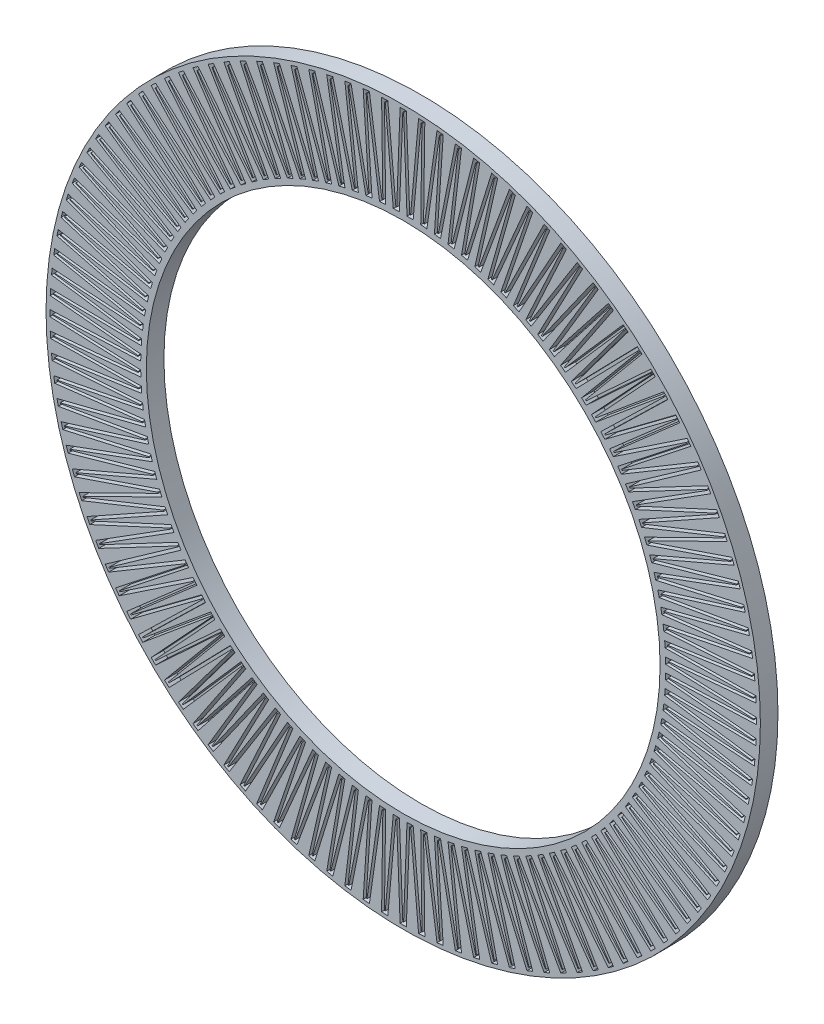
SolidWorks part; units mm, degrees
ref_plane "Front Plane" through (0, 0, 0) normal (0, 0, 1) x (1, 0, 0)
ref_plane "Top Plane" through (0, 0, 0) normal (0, 1, 0) x (1, 0, 0)
ref_plane "Right Plane" through (0, 0, 0) normal (1, 0, 0) x (0, 0, -1)
sketch "Sketch1" plane through (0, 0, 0) normal (0, 0, 1) x (1, 0, 0)
  circle A0 centre (0, 0) radius 203
  circle A1 centre (0, 0) radius 146
extrude "Ring" add sketch "Sketch1" along normal blind 10
ref_plane "Plane_z3" through (0, 0, 3) normal (0, 0, 1) x (1, 0, 0)
sketch "Sketch2" plane through (0, 0, 3) normal (0, 0, 1) x (1, 0, 0)
  line L0 (200.7975, -1.7698) -> (200.7975, 1.7698)
  line L1 (200.7975, 1.7698) -> (150.7515, 3.6974)
  line L2 (150.7515, 3.6974) -> (150.7384, 4.1974)
  line L3 (150.7384, 4.1974) -> (200.6149, 8.7416)
  line L4 (200.6149, 8.7416) -> (200.4297, 12.2763)
  line L5 (200.4297, 12.2763) -> (150.3514, 11.582)
  line L6 (150.3514, 11.582) -> (150.3122, 12.0807)
  line L7 (150.3122, 12.0807) -> (199.8825, 19.229)
  line L8 (199.8825, 19.229) -> (199.5125, 22.7491)
  line L9 (199.5125, 22.7491) -> (149.5392, 19.4349)
  line L10 (149.5392, 19.4349) -> (149.4739, 19.9309)
  line L11 (149.4739, 19.9309) -> (198.6022, 29.6637)
  line L12 (198.6022, 29.6637) -> (198.0485, 33.1596)
  line L13 (198.0485, 33.1596) -> (148.3171, 27.2346)
  line L14 (148.3171, 27.2346) -> (148.226, 27.7265)
  line L15 (148.226, 27.7265) -> (196.7776, 40.017)
  line L16 (196.7776, 40.017) -> (196.0416, 43.4793)
  line L17 (196.0416, 43.4793) -> (146.6885, 34.9596)
  line L18 (146.6885, 34.9596) -> (146.5718, 35.446)
  line L19 (146.5718, 35.446) -> (194.4135, 50.2607)
  line L20 (194.4135, 50.2607) -> (193.4974, 53.6797)
  line L21 (193.4974, 53.6797) -> (144.6579, 42.5887)
  line L22 (144.6579, 42.5887) -> (144.5158, 43.0684)
  line L23 (144.5158, 43.0684) -> (191.5167, 60.3667)
  line L24 (191.5167, 60.3667) -> (190.4229, 63.733)
  line L25 (190.4229, 63.733) -> (142.2307, 50.1012)
  line L26 (142.2307, 50.1012) -> (142.0637, 50.5727)
  line L27 (142.0637, 50.5727) -> (188.0948, 70.3072)
  line L28 (188.0948, 70.3072) -> (186.8264, 73.6116)
  line L29 (186.8264, 73.6116) -> (139.4137, 57.4763)
  line L30 (139.4137, 57.4763) -> (139.2222, 57.9385)
  line L31 (139.2222, 57.9385) -> (184.1575, 80.0549)
  line L32 (184.1575, 80.0549) -> (182.7178, 83.2885)
  line L33 (182.7178, 83.2885) -> (136.2145, 64.6939)
  line L34 (136.2145, 64.6939) -> (135.9992, 65.1454)
  line L35 (135.9992, 65.1454) -> (179.7153, 89.5833)
  line L36 (179.7153, 89.5833) -> (178.1084, 92.737)
  line L37 (178.1084, 92.737) -> (132.642, 71.7341)
  line L38 (132.642, 71.7341) -> (132.4033, 72.1738)
  line L39 (132.4033, 72.1738) -> (174.7806, 98.8661)
  line L40 (174.7806, 98.8661) -> (173.0108, 101.9314)
  line L41 (173.0108, 101.9314) -> (128.706, 78.5778)
  line L42 (128.706, 78.5778) -> (128.4446, 79.0043)
  line L43 (128.4446, 79.0043) -> (169.3668, 107.8779)
  line L44 (169.3668, 107.8779) -> (167.4391, 110.8464)
  line L45 (167.4391, 110.8464) -> (124.4172, 85.206)
  line L46 (124.4172, 85.206) -> (124.1338, 85.6183)
  line L47 (124.1338, 85.6183) -> (163.4888, 116.594)
  line L48 (163.4888, 116.594) -> (161.4083, 119.4576)
  line L49 (161.4083, 119.4576) -> (119.7873, 91.6008)
  line L50 (119.7873, 91.6008) -> (119.4828, 91.9976)
  line L51 (119.4828, 91.9976) -> (157.1627, 124.9906)
  line L52 (157.1627, 124.9906) -> (154.9352, 127.7413)
  line L53 (154.9352, 127.7413) -> (114.8291, 97.7444)
  line L54 (114.8291, 97.7444) -> (114.5042, 98.1248)
  line L55 (114.5042, 98.1248) -> (150.4058, 133.0446)
  line L56 (150.4058, 133.0446) -> (148.0374, 135.675)
  line L57 (148.0374, 135.675) -> (109.5562, 103.6201)
  line L58 (109.5562, 103.6201) -> (109.2119, 103.983)
  line L59 (109.2119, 103.983) -> (143.2367, 140.7339)
  line L60 (143.2367, 140.7339) -> (140.7339, 143.2367)
  line L61 (140.7339, 143.2367) -> (103.983, 109.2119)
  line L62 (103.983, 109.2119) -> (103.6201, 109.5562)
  line L63 (103.6201, 109.5562) -> (135.675, 148.0374)
  line L64 (135.675, 148.0374) -> (133.0446, 150.4058)
  line L65 (133.0446, 150.4058) -> (98.1248, 114.5042)
  line L66 (98.1248, 114.5042) -> (97.7444, 114.8291)
  line L67 (97.7444, 114.8291) -> (127.7413, 154.9352)
  line L68 (127.7413, 154.9352) -> (124.9906, 157.1627)
  line L69 (124.9906, 157.1627) -> (91.9976, 119.4828)
  line L70 (91.9976, 119.4828) -> (91.6008, 119.7873)
  line L71 (91.6008, 119.7873) -> (119.4576, 161.4083)
  line L72 (119.4576, 161.4083) -> (116.594, 163.4888)
  line L73 (116.594, 163.4888) -> (85.6183, 124.1338)
  line L74 (85.6183, 124.1338) -> (85.206, 124.4172)
  line L75 (85.206, 124.4172) -> (110.8464, 167.4391)
  line L76 (110.8464, 167.4391) -> (107.8779, 169.3668)
  line L77 (107.8779, 169.3668) -> (79.0043, 128.4446)
  line L78 (79.0043, 128.4446) -> (78.5778, 128.706)
  line L79 (78.5778, 128.706) -> (101.9314, 173.0108)
  line L80 (101.9314, 173.0108) -> (98.8661, 174.7806)
  line L81 (98.8661, 174.7806) -> (72.1738, 132.4033)
  line L82 (72.1738, 132.4033) -> (71.7341, 132.642)
  line L83 (71.7341, 132.642) -> (92.737, 178.1084)
  line L84 (92.737, 178.1084) -> (89.5833, 179.7153)
  line L85 (89.5833, 179.7153) -> (65.1454, 135.9992)
  line L86 (65.1454, 135.9992) -> (64.6939, 136.2145)
  line L87 (64.6939, 136.2145) -> (83.2885, 182.7178)
  line L88 (83.2885, 182.7178) -> (80.0549, 184.1575)
  line L89 (80.0549, 184.1575) -> (57.9385, 139.2222)
  line L90 (57.9385, 139.2222) -> (57.4763, 139.4137)
  line L91 (57.4763, 139.4137) -> (73.6116, 186.8264)
  line L92 (73.6116, 186.8264) -> (70.3072, 188.0948)
  line L93 (70.3072, 188.0948) -> (50.5727, 142.0637)
  line L94 (50.5727, 142.0637) -> (50.1012, 142.2307)
  line L95 (50.1012, 142.2307) -> (63.733, 190.4229)
  line L96 (63.733, 190.4229) -> (60.3667, 191.5167)
  line L97 (60.3667, 191.5167) -> (43.0684, 144.5158)
  line L98 (43.0684, 144.5158) -> (42.5887, 144.6579)
  line L99 (42.5887, 144.6579) -> (53.6797, 193.4974)
  line L100 (53.6797, 193.4974) -> (50.2607, 194.4135)
  line L101 (50.2607, 194.4135) -> (35.446, 146.5718)
  line L102 (35.446, 146.5718) -> (34.9596, 146.6885)
  line L103 (34.9596, 146.6885) -> (43.4793, 196.0416)
  line L104 (43.4793, 196.0416) -> (40.017, 196.7776)
  line L105 (40.017, 196.7776) -> (27.7265, 148.226)
  line L106 (27.7265, 148.226) -> (27.2346, 148.3171)
  line L107 (27.2346, 148.3171) -> (33.1596, 198.0485)
  line L108 (33.1596, 198.0485) -> (29.6637, 198.6022)
  line L109 (29.6637, 198.6022) -> (19.9309, 149.4739)
  line L110 (19.9309, 149.4739) -> (19.4349, 149.5392)
  line L111 (19.4349, 149.5392) -> (22.7491, 199.5125)
  line L112 (22.7491, 199.5125) -> (19.229, 199.8825)
  line L113 (19.229, 199.8825) -> (12.0807, 150.3122)
  line L114 (12.0807, 150.3122) -> (11.582, 150.3514)
  line L115 (11.582, 150.3514) -> (12.2763, 200.4297)
  line L116 (12.2763, 200.4297) -> (8.7416, 200.6149)
  line L117 (8.7416, 200.6149) -> (4.1974, 150.7384)
  line L118 (4.1974, 150.7384) -> (3.6974, 150.7515)
  line L119 (3.6974, 150.7515) -> (1.7698, 200.7975)
  line L120 (1.7698, 200.7975) -> (-1.7698, 200.7975)
  line L121 (-1.7698, 200.7975) -> (-3.6974, 150.7515)
  line L122 (-3.6974, 150.7515) -> (-4.1974, 150.7384)
  line L123 (-4.1974, 150.7384) -> (-8.7416, 200.6149)
  line L124 (-8.7416, 200.6149) -> (-12.2763, 200.4297)
  line L125 (-12.2763, 200.4297) -> (-11.582, 150.3514)
  line L126 (-11.582, 150.3514) -> (-12.0807, 150.3122)
  line L127 (-12.0807, 150.3122) -> (-19.229, 199.8825)
  line L128 (-19.229, 199.8825) -> (-22.7491, 199.5125)
  line L129 (-22.7491, 199.5125) -> (-19.4349, 149.5392)
  line L130 (-19.4349, 149.5392) -> (-19.9309, 149.4739)
  line L131 (-19.9309, 149.4739) -> (-29.6637, 198.6022)
  line L132 (-29.6637, 198.6022) -> (-33.1596, 198.0485)
  line L133 (-33.1596, 198.0485) -> (-27.2346, 148.3171)
  line L134 (-27.2346, 148.3171) -> (-27.7265, 148.226)
  line L135 (-27.7265, 148.226) -> (-40.017, 196.7776)
  line L136 (-40.017, 196.7776) -> (-43.4793, 196.0416)
  line L137 (-43.4793, 196.0416) -> (-34.9596, 146.6885)
  line L138 (-34.9596, 146.6885) -> (-35.446, 146.5718)
  line L139 (-35.446, 146.5718) -> (-50.2607, 194.4135)
  line L140 (-50.2607, 194.4135) -> (-53.6797, 193.4974)
  line L141 (-53.6797, 193.4974) -> (-42.5887, 144.6579)
  line L142 (-42.5887, 144.6579) -> (-43.0684, 144.5158)
  line L143 (-43.0684, 144.5158) -> (-60.3667, 191.5167)
  line L144 (-60.3667, 191.5167) -> (-63.733, 190.4229)
  line L145 (-63.733, 190.4229) -> (-50.1012, 142.2307)
  line L146 (-50.1012, 142.2307) -> (-50.5727, 142.0637)
  line L147 (-50.5727, 142.0637) -> (-70.3072, 188.0948)
  line L148 (-70.3072, 188.0948) -> (-73.6116, 186.8264)
  line L149 (-73.6116, 186.8264) -> (-57.4763, 139.4137)
  line L150 (-57.4763, 139.4137) -> (-57.9385, 139.2222)
  line L151 (-57.9385, 139.2222) -> (-80.0549, 184.1575)
  line L152 (-80.0549, 184.1575) -> (-83.2885, 182.7178)
  line L153 (-83.2885, 182.7178) -> (-64.6939, 136.2145)
  line L154 (-64.6939, 136.2145) -> (-65.1454, 135.9992)
  line L155 (-65.1454, 135.9992) -> (-89.5833, 179.7153)
  line L156 (-89.5833, 179.7153) -> (-92.737, 178.1084)
  line L157 (-92.737, 178.1084) -> (-71.7341, 132.642)
  line L158 (-71.7341, 132.642) -> (-72.1738, 132.4033)
  line L159 (-72.1738, 132.4033) -> (-98.8661, 174.7806)
  line L160 (-98.8661, 174.7806) -> (-101.9314, 173.0108)
  line L161 (-101.9314, 173.0108) -> (-78.5778, 128.706)
  line L162 (-78.5778, 128.706) -> (-79.0043, 128.4446)
  line L163 (-79.0043, 128.4446) -> (-107.8779, 169.3668)
  line L164 (-107.8779, 169.3668) -> (-110.8464, 167.4391)
  line L165 (-110.8464, 167.4391) -> (-85.206, 124.4172)
  line L166 (-85.206, 124.4172) -> (-85.6183, 124.1338)
  line L167 (-85.6183, 124.1338) -> (-116.594, 163.4888)
  line L168 (-116.594, 163.4888) -> (-119.4576, 161.4083)
  line L169 (-119.4576, 161.4083) -> (-91.6008, 119.7873)
  line L170 (-91.6008, 119.7873) -> (-91.9976, 119.4828)
  line L171 (-91.9976, 119.4828) -> (-124.9906, 157.1627)
  line L172 (-124.9906, 157.1627) -> (-127.7413, 154.9352)
  line L173 (-127.7413, 154.9352) -> (-97.7444, 114.8291)
  line L174 (-97.7444, 114.8291) -> (-98.1248, 114.5042)
  line L175 (-98.1248, 114.5042) -> (-133.0446, 150.4058)
  line L176 (-133.0446, 150.4058) -> (-135.675, 148.0374)
  line L177 (-135.675, 148.0374) -> (-103.6201, 109.5562)
  line L178 (-103.6201, 109.5562) -> (-103.983, 109.2119)
  line L179 (-103.983, 109.2119) -> (-140.7339, 143.2367)
  line L180 (-140.7339, 143.2367) -> (-143.2367, 140.7339)
  line L181 (-143.2367, 140.7339) -> (-109.2119, 103.983)
  line L182 (-109.2119, 103.983) -> (-109.5562, 103.6201)
  line L183 (-109.5562, 103.6201) -> (-148.0374, 135.675)
  line L184 (-148.0374, 135.675) -> (-150.4058, 133.0446)
  line L185 (-150.4058, 133.0446) -> (-114.5042, 98.1248)
  line L186 (-114.5042, 98.1248) -> (-114.8291, 97.7444)
  line L187 (-114.8291, 97.7444) -> (-154.9352, 127.7413)
  line L188 (-154.9352, 127.7413) -> (-157.1627, 124.9906)
  line L189 (-157.1627, 124.9906) -> (-119.4828, 91.9976)
  line L190 (-119.4828, 91.9976) -> (-119.7873, 91.6008)
  line L191 (-119.7873, 91.6008) -> (-161.4083, 119.4576)
  line L192 (-161.4083, 119.4576) -> (-163.4888, 116.594)
  line L193 (-163.4888, 116.594) -> (-124.1338, 85.6183)
  line L194 (-124.1338, 85.6183) -> (-124.4172, 85.206)
  line L195 (-124.4172, 85.206) -> (-167.4391, 110.8464)
  line L196 (-167.4391, 110.8464) -> (-169.3668, 107.8779)
  line L197 (-169.3668, 107.8779) -> (-128.4446, 79.0043)
  line L198 (-128.4446, 79.0043) -> (-128.706, 78.5778)
  line L199 (-128.706, 78.5778) -> (-173.0108, 101.9314)
  line L200 (-173.0108, 101.9314) -> (-174.7806, 98.8661)
  line L201 (-174.7806, 98.8661) -> (-132.4033, 72.1738)
  line L202 (-132.4033, 72.1738) -> (-132.642, 71.7341)
  line L203 (-132.642, 71.7341) -> (-178.1084, 92.737)
  line L204 (-178.1084, 92.737) -> (-179.7153, 89.5833)
  line L205 (-179.7153, 89.5833) -> (-135.9992, 65.1454)
  line L206 (-135.9992, 65.1454) -> (-136.2145, 64.6939)
  line L207 (-136.2145, 64.6939) -> (-182.7178, 83.2885)
  line L208 (-182.7178, 83.2885) -> (-184.1575, 80.0549)
  line L209 (-184.1575, 80.0549) -> (-139.2222, 57.9385)
  line L210 (-139.2222, 57.9385) -> (-139.4137, 57.4763)
  line L211 (-139.4137, 57.4763) -> (-186.8264, 73.6116)
  line L212 (-186.8264, 73.6116) -> (-188.0948, 70.3072)
  line L213 (-188.0948, 70.3072) -> (-142.0637, 50.5727)
  line L214 (-142.0637, 50.5727) -> (-142.2307, 50.1012)
  line L215 (-142.2307, 50.1012) -> (-190.4229, 63.733)
  line L216 (-190.4229, 63.733) -> (-191.5167, 60.3667)
  line L217 (-191.5167, 60.3667) -> (-144.5158, 43.0684)
  line L218 (-144.5158, 43.0684) -> (-144.6579, 42.5887)
  line L219 (-144.6579, 42.5887) -> (-193.4974, 53.6797)
  line L220 (-193.4974, 53.6797) -> (-194.4135, 50.2607)
  line L221 (-194.4135, 50.2607) -> (-146.5718, 35.446)
  line L222 (-146.5718, 35.446) -> (-146.6885, 34.9596)
  line L223 (-146.6885, 34.9596) -> (-196.0416, 43.4793)
  line L224 (-196.0416, 43.4793) -> (-196.7776, 40.017)
  line L225 (-196.7776, 40.017) -> (-148.226, 27.7265)
  line L226 (-148.226, 27.7265) -> (-148.3171, 27.2346)
  line L227 (-148.3171, 27.2346) -> (-198.0485, 33.1596)
  line L228 (-198.0485, 33.1596) -> (-198.6022, 29.6637)
  line L229 (-198.6022, 29.6637) -> (-149.4739, 19.9309)
  line L230 (-149.4739, 19.9309) -> (-149.5392, 19.4349)
  line L231 (-149.5392, 19.4349) -> (-199.5125, 22.7491)
  line L232 (-199.5125, 22.7491) -> (-199.8825, 19.229)
  line L233 (-199.8825, 19.229) -> (-150.3122, 12.0807)
  line L234 (-150.3122, 12.0807) -> (-150.3514, 11.582)
  line L235 (-150.3514, 11.582) -> (-200.4297, 12.2763)
  line L236 (-200.4297, 12.2763) -> (-200.6149, 8.7416)
  line L237 (-200.6149, 8.7416) -> (-150.7384, 4.1974)
  line L238 (-150.7384, 4.1974) -> (-150.7515, 3.6974)
  line L239 (-150.7515, 3.6974) -> (-200.7975, 1.7698)
  line L240 (-200.7975, 1.7698) -> (-200.7975, -1.7698)
  line L241 (-200.7975, -1.7698) -> (-150.7515, -3.6974)
  line L242 (-150.7515, -3.6974) -> (-150.7384, -4.1974)
  line L243 (-150.7384, -4.1974) -> (-200.6149, -8.7416)
  line L244 (-200.6149, -8.7416) -> (-200.4297, -12.2763)
  line L245 (-200.4297, -12.2763) -> (-150.3514, -11.582)
  line L246 (-150.3514, -11.582) -> (-150.3122, -12.0807)
  line L247 (-150.3122, -12.0807) -> (-199.8825, -19.229)
  line L248 (-199.8825, -19.229) -> (-199.5125, -22.7491)
  line L249 (-199.5125, -22.7491) -> (-149.5392, -19.4349)
  line L250 (-149.5392, -19.4349) -> (-149.4739, -19.9309)
  line L251 (-149.4739, -19.9309) -> (-198.6022, -29.6637)
  line L252 (-198.6022, -29.6637) -> (-198.0485, -33.1596)
  line L253 (-198.0485, -33.1596) -> (-148.3171, -27.2346)
  line L254 (-148.3171, -27.2346) -> (-148.226, -27.7265)
  line L255 (-148.226, -27.7265) -> (-196.7776, -40.017)
  line L256 (-196.7776, -40.017) -> (-196.0416, -43.4793)
  line L257 (-196.0416, -43.4793) -> (-146.6885, -34.9596)
  line L258 (-146.6885, -34.9596) -> (-146.5718, -35.446)
  line L259 (-146.5718, -35.446) -> (-194.4135, -50.2607)
  line L260 (-194.4135, -50.2607) -> (-193.4974, -53.6797)
  line L261 (-193.4974, -53.6797) -> (-144.6579, -42.5887)
  line L262 (-144.6579, -42.5887) -> (-144.5158, -43.0684)
  line L263 (-144.5158, -43.0684) -> (-191.5167, -60.3667)
  line L264 (-191.5167, -60.3667) -> (-190.4229, -63.733)
  line L265 (-190.4229, -63.733) -> (-142.2307, -50.1012)
  line L266 (-142.2307, -50.1012) -> (-142.0637, -50.5727)
  line L267 (-142.0637, -50.5727) -> (-188.0948, -70.3072)
  line L268 (-188.0948, -70.3072) -> (-186.8264, -73.6116)
  line L269 (-186.8264, -73.6116) -> (-139.4137, -57.4763)
  line L270 (-139.4137, -57.4763) -> (-139.2222, -57.9385)
  line L271 (-139.2222, -57.9385) -> (-184.1575, -80.0549)
  line L272 (-184.1575, -80.0549) -> (-182.7178, -83.2885)
  line L273 (-182.7178, -83.2885) -> (-136.2145, -64.6939)
  line L274 (-136.2145, -64.6939) -> (-135.9992, -65.1454)
  line L275 (-135.9992, -65.1454) -> (-179.7153, -89.5833)
  line L276 (-179.7153, -89.5833) -> (-178.1084, -92.737)
  line L277 (-178.1084, -92.737) -> (-132.642, -71.7341)
  line L278 (-132.642, -71.7341) -> (-132.4033, -72.1738)
  line L279 (-132.4033, -72.1738) -> (-174.7806, -98.8661)
  line L280 (-174.7806, -98.8661) -> (-173.0108, -101.9314)
  line L281 (-173.0108, -101.9314) -> (-128.706, -78.5778)
  line L282 (-128.706, -78.5778) -> (-128.4446, -79.0043)
  line L283 (-128.4446, -79.0043) -> (-169.3668, -107.8779)
  line L284 (-169.3668, -107.8779) -> (-167.4391, -110.8464)
  line L285 (-167.4391, -110.8464) -> (-124.4172, -85.206)
  line L286 (-124.4172, -85.206) -> (-124.1338, -85.6183)
  line L287 (-124.1338, -85.6183) -> (-163.4888, -116.594)
  line L288 (-163.4888, -116.594) -> (-161.4083, -119.4576)
  line L289 (-161.4083, -119.4576) -> (-119.7873, -91.6008)
  line L290 (-119.7873, -91.6008) -> (-119.4828, -91.9976)
  line L291 (-119.4828, -91.9976) -> (-157.1627, -124.9906)
  line L292 (-157.1627, -124.9906) -> (-154.9352, -127.7413)
  line L293 (-154.9352, -127.7413) -> (-114.8291, -97.7444)
  line L294 (-114.8291, -97.7444) -> (-114.5042, -98.1248)
  line L295 (-114.5042, -98.1248) -> (-150.4058, -133.0446)
  line L296 (-150.4058, -133.0446) -> (-148.0374, -135.675)
  line L297 (-148.0374, -135.675) -> (-109.5562, -103.6201)
  line L298 (-109.5562, -103.6201) -> (-109.2119, -103.983)
  line L299 (-109.2119, -103.983) -> (-143.2367, -140.7339)
  line L300 (-143.2367, -140.7339) -> (-140.7339, -143.2367)
  line L301 (-140.7339, -143.2367) -> (-103.983, -109.2119)
  line L302 (-103.983, -109.2119) -> (-103.6201, -109.5562)
  line L303 (-103.6201, -109.5562) -> (-135.675, -148.0374)
  line L304 (-135.675, -148.0374) -> (-133.0446, -150.4058)
  line L305 (-133.0446, -150.4058) -> (-98.1248, -114.5042)
  line L306 (-98.1248, -114.5042) -> (-97.7444, -114.8291)
  line L307 (-97.7444, -114.8291) -> (-127.7413, -154.9352)
  line L308 (-127.7413, -154.9352) -> (-124.9906, -157.1627)
  line L309 (-124.9906, -157.1627) -> (-91.9976, -119.4828)
  line L310 (-91.9976, -119.4828) -> (-91.6008, -119.7873)
  line L311 (-91.6008, -119.7873) -> (-119.4576, -161.4083)
  line L312 (-119.4576, -161.4083) -> (-116.594, -163.4888)
  line L313 (-116.594, -163.4888) -> (-85.6183, -124.1338)
  line L314 (-85.6183, -124.1338) -> (-85.206, -124.4172)
  line L315 (-85.206, -124.4172) -> (-110.8464, -167.4391)
  line L316 (-110.8464, -167.4391) -> (-107.8779, -169.3668)
  line L317 (-107.8779, -169.3668) -> (-79.0043, -128.4446)
  line L318 (-79.0043, -128.4446) -> (-78.5778, -128.706)
  line L319 (-78.5778, -128.706) -> (-101.9314, -173.0108)
  line L320 (-101.9314, -173.0108) -> (-98.8661, -174.7806)
  line L321 (-98.8661, -174.7806) -> (-72.1738, -132.4033)
  line L322 (-72.1738, -132.4033) -> (-71.7341, -132.642)
  line L323 (-71.7341, -132.642) -> (-92.737, -178.1084)
  line L324 (-92.737, -178.1084) -> (-89.5833, -179.7153)
  line L325 (-89.5833, -179.7153) -> (-65.1454, -135.9992)
  line L326 (-65.1454, -135.9992) -> (-64.6939, -136.2145)
  line L327 (-64.6939, -136.2145) -> (-83.2885, -182.7178)
  line L328 (-83.2885, -182.7178) -> (-80.0549, -184.1575)
  line L329 (-80.0549, -184.1575) -> (-57.9385, -139.2222)
  line L330 (-57.9385, -139.2222) -> (-57.4763, -139.4137)
  line L331 (-57.4763, -139.4137) -> (-73.6116, -186.8264)
  line L332 (-73.6116, -186.8264) -> (-70.3072, -188.0948)
  line L333 (-70.3072, -188.0948) -> (-50.5727, -142.0637)
  line L334 (-50.5727, -142.0637) -> (-50.1012, -142.2307)
  line L335 (-50.1012, -142.2307) -> (-63.733, -190.4229)
  line L336 (-63.733, -190.4229) -> (-60.3667, -191.5167)
  line L337 (-60.3667, -191.5167) -> (-43.0684, -144.5158)
  line L338 (-43.0684, -144.5158) -> (-42.5887, -144.6579)
  line L339 (-42.5887, -144.6579) -> (-53.6797, -193.4974)
  line L340 (-53.6797, -193.4974) -> (-50.2607, -194.4135)
  line L341 (-50.2607, -194.4135) -> (-35.446, -146.5718)
  line L342 (-35.446, -146.5718) -> (-34.9596, -146.6885)
  line L343 (-34.9596, -146.6885) -> (-43.4793, -196.0416)
  line L344 (-43.4793, -196.0416) -> (-40.017, -196.7776)
  line L345 (-40.017, -196.7776) -> (-27.7265, -148.226)
  line L346 (-27.7265, -148.226) -> (-27.2346, -148.3171)
  line L347 (-27.2346, -148.3171) -> (-33.1596, -198.0485)
  line L348 (-33.1596, -198.0485) -> (-29.6637, -198.6022)
  line L349 (-29.6637, -198.6022) -> (-19.9309, -149.4739)
  line L350 (-19.9309, -149.4739) -> (-19.4349, -149.5392)
  line L351 (-19.4349, -149.5392) -> (-22.7491, -199.5125)
  line L352 (-22.7491, -199.5125) -> (-19.229, -199.8825)
  line L353 (-19.229, -199.8825) -> (-12.0807, -150.3122)
  line L354 (-12.0807, -150.3122) -> (-11.582, -150.3514)
  line L355 (-11.582, -150.3514) -> (-12.2763, -200.4297)
  line L356 (-12.2763, -200.4297) -> (-8.7416, -200.6149)
  line L357 (-8.7416, -200.6149) -> (-4.1974, -150.7384)
  line L358 (-4.1974, -150.7384) -> (-3.6974, -150.7515)
  line L359 (-3.6974, -150.7515) -> (-1.7698, -200.7975)
  line L360 (-1.7698, -200.7975) -> (1.7698, -200.7975)
  line L361 (1.7698, -200.7975) -> (3.6974, -150.7515)
  line L362 (3.6974, -150.7515) -> (4.1974, -150.7384)
  line L363 (4.1974, -150.7384) -> (8.7416, -200.6149)
  line L364 (8.7416, -200.6149) -> (12.2763, -200.4297)
  line L365 (12.2763, -200.4297) -> (11.582, -150.3514)
  line L366 (11.582, -150.3514) -> (12.0807, -150.3122)
  line L367 (12.0807, -150.3122) -> (19.229, -199.8825)
  line L368 (19.229, -199.8825) -> (22.7491, -199.5125)
  line L369 (22.7491, -199.5125) -> (19.4349, -149.5392)
  line L370 (19.4349, -149.5392) -> (19.9309, -149.4739)
  line L371 (19.9309, -149.4739) -> (29.6637, -198.6022)
  line L372 (29.6637, -198.6022) -> (33.1596, -198.0485)
  line L373 (33.1596, -198.0485) -> (27.2346, -148.3171)
  line L374 (27.2346, -148.3171) -> (27.7265, -148.226)
  line L375 (27.7265, -148.226) -> (40.017, -196.7776)
  line L376 (40.017, -196.7776) -> (43.4793, -196.0416)
  line L377 (43.4793, -196.0416) -> (34.9596, -146.6885)
  line L378 (34.9596, -146.6885) -> (35.446, -146.5718)
  line L379 (35.446, -146.5718) -> (50.2607, -194.4135)
  line L380 (50.2607, -194.4135) -> (53.6797, -193.4974)
  line L381 (53.6797, -193.4974) -> (42.5887, -144.6579)
  line L382 (42.5887, -144.6579) -> (43.0684, -144.5158)
  line L383 (43.0684, -144.5158) -> (60.3667, -191.5167)
  line L384 (60.3667, -191.5167) -> (63.733, -190.4229)
  line L385 (63.733, -190.4229) -> (50.1012, -142.2307)
  line L386 (50.1012, -142.2307) -> (50.5727, -142.0637)
  line L387 (50.5727, -142.0637) -> (70.3072, -188.0948)
  line L388 (70.3072, -188.0948) -> (73.6116, -186.8264)
  line L389 (73.6116, -186.8264) -> (57.4763, -139.4137)
  line L390 (57.4763, -139.4137) -> (57.9385, -139.2222)
  line L391 (57.9385, -139.2222) -> (80.0549, -184.1575)
  line L392 (80.0549, -184.1575) -> (83.2885, -182.7178)
  line L393 (83.2885, -182.7178) -> (64.6939, -136.2145)
  line L394 (64.6939, -136.2145) -> (65.1454, -135.9992)
  line L395 (65.1454, -135.9992) -> (89.5833, -179.7153)
  line L396 (89.5833, -179.7153) -> (92.737, -178.1084)
  line L397 (92.737, -178.1084) -> (71.7341, -132.642)
  line L398 (71.7341, -132.642) -> (72.1738, -132.4033)
  line L399 (72.1738, -132.4033) -> (98.8661, -174.7806)
  line L400 (98.8661, -174.7806) -> (101.9314, -173.0108)
  line L401 (101.9314, -173.0108) -> (78.5778, -128.706)
  line L402 (78.5778, -128.706) -> (79.0043, -128.4446)
  line L403 (79.0043, -128.4446) -> (107.8779, -169.3668)
  line L404 (107.8779, -169.3668) -> (110.8464, -167.4391)
  line L405 (110.8464, -167.4391) -> (85.206, -124.4172)
  line L406 (85.206, -124.4172) -> (85.6183, -124.1338)
  line L407 (85.6183, -124.1338) -> (116.594, -163.4888)
  line L408 (116.594, -163.4888) -> (119.4576, -161.4083)
  line L409 (119.4576, -161.4083) -> (91.6008, -119.7873)
  line L410 (91.6008, -119.7873) -> (91.9976, -119.4828)
  line L411 (91.9976, -119.4828) -> (124.9906, -157.1627)
  line L412 (124.9906, -157.1627) -> (127.7413, -154.9352)
  line L413 (127.7413, -154.9352) -> (97.7444, -114.8291)
  line L414 (97.7444, -114.8291) -> (98.1248, -114.5042)
  line L415 (98.1248, -114.5042) -> (133.0446, -150.4058)
  line L416 (133.0446, -150.4058) -> (135.675, -148.0374)
  line L417 (135.675, -148.0374) -> (103.6201, -109.5562)
  line L418 (103.6201, -109.5562) -> (103.983, -109.2119)
  line L419 (103.983, -109.2119) -> (140.7339, -143.2367)
  line L420 (140.7339, -143.2367) -> (143.2367, -140.7339)
  line L421 (143.2367, -140.7339) -> (109.2119, -103.983)
  line L422 (109.2119, -103.983) -> (109.5562, -103.6201)
  line L423 (109.5562, -103.6201) -> (148.0374, -135.675)
  line L424 (148.0374, -135.675) -> (150.4058, -133.0446)
  line L425 (150.4058, -133.0446) -> (114.5042, -98.1248)
  line L426 (114.5042, -98.1248) -> (114.8291, -97.7444)
  line L427 (114.8291, -97.7444) -> (154.9352, -127.7413)
  line L428 (154.9352, -127.7413) -> (157.1627, -124.9906)
  line L429 (157.1627, -124.9906) -> (119.4828, -91.9976)
  line L430 (119.4828, -91.9976) -> (119.7873, -91.6008)
  line L431 (119.7873, -91.6008) -> (161.4083, -119.4576)
  line L432 (161.4083, -119.4576) -> (163.4888, -116.594)
  line L433 (163.4888, -116.594) -> (124.1338, -85.6183)
  line L434 (124.1338, -85.6183) -> (124.4172, -85.206)
  line L435 (124.4172, -85.206) -> (167.4391, -110.8464)
  line L436 (167.4391, -110.8464) -> (169.3668, -107.8779)
  line L437 (169.3668, -107.8779) -> (128.4446, -79.0043)
  line L438 (128.4446, -79.0043) -> (128.706, -78.5778)
  line L439 (128.706, -78.5778) -> (173.0108, -101.9314)
  line L440 (173.0108, -101.9314) -> (174.7806, -98.8661)
  line L441 (174.7806, -98.8661) -> (132.4033, -72.1738)
  line L442 (132.4033, -72.1738) -> (132.642, -71.7341)
  line L443 (132.642, -71.7341) -> (178.1084, -92.737)
  line L444 (178.1084, -92.737) -> (179.7153, -89.5833)
  line L445 (179.7153, -89.5833) -> (135.9992, -65.1454)
  line L446 (135.9992, -65.1454) -> (136.2145, -64.6939)
  line L447 (136.2145, -64.6939) -> (182.7178, -83.2885)
  line L448 (182.7178, -83.2885) -> (184.1575, -80.0549)
  line L449 (184.1575, -80.0549) -> (139.2222, -57.9385)
  line L450 (139.2222, -57.9385) -> (139.4137, -57.4763)
  line L451 (139.4137, -57.4763) -> (186.8264, -73.6116)
  line L452 (186.8264, -73.6116) -> (188.0948, -70.3072)
  line L453 (188.0948, -70.3072) -> (142.0637, -50.5727)
  line L454 (142.0637, -50.5727) -> (142.2307, -50.1012)
  line L455 (142.2307, -50.1012) -> (190.4229, -63.733)
  line L456 (190.4229, -63.733) -> (191.5167, -60.3667)
  line L457 (191.5167, -60.3667) -> (144.5158, -43.0684)
  line L458 (144.5158, -43.0684) -> (144.6579, -42.5887)
  line L459 (144.6579, -42.5887) -> (193.4974, -53.6797)
  line L460 (193.4974, -53.6797) -> (194.4135, -50.2607)
  line L461 (194.4135, -50.2607) -> (146.5718, -35.446)
  line L462 (146.5718, -35.446) -> (146.6885, -34.9596)
  line L463 (146.6885, -34.9596) -> (196.0416, -43.4793)
  line L464 (196.0416, -43.4793) -> (196.7776, -40.017)
  line L465 (196.7776, -40.017) -> (148.226, -27.7265)
  line L466 (148.226, -27.7265) -> (148.3171, -27.2346)
  line L467 (148.3171, -27.2346) -> (198.0485, -33.1596)
  line L468 (198.0485, -33.1596) -> (198.6022, -29.6637)
  line L469 (198.6022, -29.6637) -> (149.4739, -19.9309)
  line L470 (149.4739, -19.9309) -> (149.5392, -19.4349)
  line L471 (149.5392, -19.4349) -> (199.5125, -22.7491)
  line L472 (199.5125, -22.7491) -> (199.8825, -19.229)
  line L473 (199.8825, -19.229) -> (150.3122, -12.0807)
  line L474 (150.3122, -12.0807) -> (150.3514, -11.582)
  line L475 (150.3514, -11.582) -> (200.4297, -12.2763)
  line L476 (200.4297, -12.2763) -> (200.6149, -8.7416)
  line L477 (200.6149, -8.7416) -> (150.7384, -4.1974)
  line L478 (150.7384, -4.1974) -> (150.7515, -3.6974)
  line L479 (150.7515, -3.6974) -> (200.7975, -1.7698)
  line L480 (199.1975, -0.2302) -> (199.1975, 0.2302)
  line L481 (199.1975, 0.2302) -> (149.1913, 2.1563)
  line L482 (149.1913, 2.1563) -> (149.0997, 5.6548)
  line L483 (149.0997, 5.6548) -> (198.9366, 10.1953)
  line L484 (198.9366, 10.1953) -> (198.9125, 10.6551)
  line L485 (198.9125, 10.6551) -> (148.874, 9.9614)
  line L486 (148.874, 9.9614) -> (148.5995, 13.4503)
  line L487 (148.5995, 13.4503) -> (198.1303, 20.5929)
  line L488 (198.1303, 20.5929) -> (198.0822, 21.0508)
  line L489 (198.0822, 21.0508) -> (148.1487, 17.7392)
  line L490 (148.1487, 17.7392) -> (147.6919, 21.209)
  line L491 (147.6919, 21.209) -> (196.7811, 30.934)
  line L492 (196.7811, 30.934) -> (196.709, 31.3887)
  line L493 (196.709, 31.3887) -> (147.0172, 25.4684)
  line L494 (147.0172, 25.4684) -> (146.3795, 28.9095)
  line L495 (146.3795, 28.9095) -> (194.8924, 41.1903)
  line L496 (194.8924, 41.1903) -> (194.7967, 41.6407)
  line L497 (194.7967, 41.6407) -> (145.4828, 33.1278)
  line L498 (145.4828, 33.1278) -> (144.6659, 36.5308)
  line L499 (144.6659, 36.5308) -> (192.4696, 51.3337)
  line L500 (192.4696, 51.3337) -> (192.3504, 51.7785)
  line L501 (192.3504, 51.7785) -> (143.5497, 40.6963)
  line L502 (143.5497, 40.6963) -> (142.5557, 44.0519)
  line L503 (142.5557, 44.0519) -> (189.5192, 61.3365)
  line L504 (189.5192, 61.3365) -> (189.3769, 61.7744)
  line L505 (189.3769, 61.7744) -> (141.2231, 48.1534)
  line L506 (141.2231, 48.1534) -> (140.0549, 51.4524)
  line L507 (140.0549, 51.4524) -> (186.0494, 71.1711)
  line L508 (186.0494, 71.1711) -> (185.8844, 71.6009)
  line L509 (185.8844, 71.6009) -> (138.5094, 55.4784)
  line L510 (138.5094, 55.4784) -> (137.1701, 58.7117)
  line L511 (137.1701, 58.7117) -> (182.0696, 80.8106)
  line L512 (182.0696, 80.8106) -> (181.8823, 81.2312)
  line L513 (181.8823, 81.2312) -> (135.416, 62.6514)
  line L514 (135.416, 62.6514) -> (133.9094, 65.8102)
  line L515 (133.9094, 65.8102) -> (177.5908, 90.2286)
  line L516 (177.5908, 90.2286) -> (177.3818, 90.6389)
  line L517 (177.3818, 90.6389) -> (131.9515, 69.6527)
  line L518 (131.9515, 69.6527) -> (130.2816, 72.7283)
  line L519 (130.2816, 72.7283) -> (172.6252, 99.3994)
  line L520 (172.6252, 99.3994) -> (172.395, 99.7981)
  line L521 (172.395, 99.7981) -> (128.1254, 76.463)
  line L522 (128.1254, 76.463) -> (126.2968, 79.447)
  line L523 (126.2968, 79.447) -> (167.1865, 108.2977)
  line L524 (167.1865, 108.2977) -> (166.9357, 108.6838)
  line L525 (166.9357, 108.6838) -> (123.948, 83.0638)
  line L526 (123.948, 83.0638) -> (121.9658, 85.948)
  line L527 (121.9658, 85.948) -> (161.2895, 116.8991)
  line L528 (161.2895, 116.8991) -> (161.0188, 117.2716)
  line L529 (161.0188, 117.2716) -> (119.4309, 89.4369)
  line L530 (119.4309, 89.4369) -> (117.3004, 92.2134)
  line L531 (117.3004, 92.2134) -> (154.9504, 125.1801)
  line L532 (154.9504, 125.1801) -> (154.6607, 125.538)
  line L533 (154.6607, 125.538) -> (114.5865, 95.5649)
  line L534 (114.5865, 95.5649) -> (112.3136, 98.2261)
  line L535 (112.3136, 98.2261) -> (148.1866, 133.1181)
  line L536 (148.1866, 133.1181) -> (147.8785, 133.4602)
  line L537 (147.8785, 133.4602) -> (109.428, 101.4309)
  line L538 (109.428, 101.4309) -> (107.0189, 103.9695)
  line L539 (107.0189, 103.9695) -> (141.0167, 140.6911)
  line L540 (141.0167, 140.6911) -> (140.6911, 141.0167)
  line L541 (140.6911, 141.0167) -> (103.9695, 107.0189)
  line L542 (103.9695, 107.0189) -> (101.4309, 109.428)
  line L543 (101.4309, 109.428) -> (133.4602, 147.8785)
  line L544 (133.4602, 147.8785) -> (133.1181, 148.1866)
  line L545 (133.1181, 148.1866) -> (98.2261, 112.3136)
  line L546 (98.2261, 112.3136) -> (95.5649, 114.5865)
  line L547 (95.5649, 114.5865) -> (125.538, 154.6607)
  line L548 (125.538, 154.6607) -> (125.1801, 154.9504)
  line L549 (125.1801, 154.9504) -> (92.2134, 117.3004)
  line L550 (92.2134, 117.3004) -> (89.4369, 119.4309)
  line L551 (89.4369, 119.4309) -> (117.2716, 161.0188)
  line L552 (117.2716, 161.0188) -> (116.8991, 161.2895)
  line L553 (116.8991, 161.2895) -> (85.948, 121.9658)
  line L554 (85.948, 121.9658) -> (83.0638, 123.948)
  line L555 (83.0638, 123.948) -> (108.6838, 166.9357)
  line L556 (108.6838, 166.9357) -> (108.2977, 167.1865)
  line L557 (108.2977, 167.1865) -> (79.447, 126.2968)
  line L558 (79.447, 126.2968) -> (76.463, 128.1254)
  line L559 (76.463, 128.1254) -> (99.7981, 172.395)
  line L560 (99.7981, 172.395) -> (99.3994, 172.6252)
  line L561 (99.3994, 172.6252) -> (72.7283, 130.2816)
  line L562 (72.7283, 130.2816) -> (69.6527, 131.9515)
  line L563 (69.6527, 131.9515) -> (90.6389, 177.3818)
  line L564 (90.6389, 177.3818) -> (90.2286, 177.5908)
  line L565 (90.2286, 177.5908) -> (65.8102, 133.9094)
  line L566 (65.8102, 133.9094) -> (62.6514, 135.416)
  line L567 (62.6514, 135.416) -> (81.2312, 181.8823)
  line L568 (81.2312, 181.8823) -> (80.8106, 182.0696)
  line L569 (80.8106, 182.0696) -> (58.7117, 137.1701)
  line L570 (58.7117, 137.1701) -> (55.4784, 138.5094)
  line L571 (55.4784, 138.5094) -> (71.6009, 185.8844)
  line L572 (71.6009, 185.8844) -> (71.1711, 186.0494)
  line L573 (71.1711, 186.0494) -> (51.4524, 140.0549)
  line L574 (51.4524, 140.0549) -> (48.1534, 141.2231)
  line L575 (48.1534, 141.2231) -> (61.7744, 189.3769)
  line L576 (61.7744, 189.3769) -> (61.3365, 189.5192)
  line L577 (61.3365, 189.5192) -> (44.0519, 142.5557)
  line L578 (44.0519, 142.5557) -> (40.6963, 143.5497)
  line L579 (40.6963, 143.5497) -> (51.7785, 192.3504)
  line L580 (51.7785, 192.3504) -> (51.3337, 192.4696)
  line L581 (51.3337, 192.4696) -> (36.5308, 144.6659)
  line L582 (36.5308, 144.6659) -> (33.1278, 145.4828)
  line L583 (33.1278, 145.4828) -> (41.6407, 194.7967)
  line L584 (41.6407, 194.7967) -> (41.1903, 194.8924)
  line L585 (41.1903, 194.8924) -> (28.9095, 146.3795)
  line L586 (28.9095, 146.3795) -> (25.4684, 147.0172)
  line L587 (25.4684, 147.0172) -> (31.3887, 196.709)
  line L588 (31.3887, 196.709) -> (30.934, 196.7811)
  line L589 (30.934, 196.7811) -> (21.209, 147.6919)
  line L590 (21.209, 147.6919) -> (17.7392, 148.1487)
  line L591 (17.7392, 148.1487) -> (21.0508, 198.0822)
  line L592 (21.0508, 198.0822) -> (20.5929, 198.1303)
  line L593 (20.5929, 198.1303) -> (13.4503, 148.5995)
  line L594 (13.4503, 148.5995) -> (9.9614, 148.874)
  line L595 (9.9614, 148.874) -> (10.6551, 198.9125)
  line L596 (10.6551, 198.9125) -> (10.1953, 198.9366)
  line L597 (10.1953, 198.9366) -> (5.6548, 149.0997)
  line L598 (5.6548, 149.0997) -> (2.1563, 149.1913)
  line L599 (2.1563, 149.1913) -> (0.2302, 199.1975)
  line L600 (0.2302, 199.1975) -> (-0.2302, 199.1975)
  line L601 (-0.2302, 199.1975) -> (-2.1563, 149.1913)
  line L602 (-2.1563, 149.1913) -> (-5.6548, 149.0997)
  line L603 (-5.6548, 149.0997) -> (-10.1953, 198.9366)
  line L604 (-10.1953, 198.9366) -> (-10.6551, 198.9125)
  line L605 (-10.6551, 198.9125) -> (-9.9614, 148.874)
  line L606 (-9.9614, 148.874) -> (-13.4503, 148.5995)
  line L607 (-13.4503, 148.5995) -> (-20.5929, 198.1303)
  line L608 (-20.5929, 198.1303) -> (-21.0508, 198.0822)
  line L609 (-21.0508, 198.0822) -> (-17.7392, 148.1487)
  line L610 (-17.7392, 148.1487) -> (-21.209, 147.6919)
  line L611 (-21.209, 147.6919) -> (-30.934, 196.7811)
  line L612 (-30.934, 196.7811) -> (-31.3887, 196.709)
  line L613 (-31.3887, 196.709) -> (-25.4684, 147.0172)
  line L614 (-25.4684, 147.0172) -> (-28.9095, 146.3795)
  line L615 (-28.9095, 146.3795) -> (-41.1903, 194.8924)
  line L616 (-41.1903, 194.8924) -> (-41.6407, 194.7967)
  line L617 (-41.6407, 194.7967) -> (-33.1278, 145.4828)
  line L618 (-33.1278, 145.4828) -> (-36.5308, 144.6659)
  line L619 (-36.5308, 144.6659) -> (-51.3337, 192.4696)
  line L620 (-51.3337, 192.4696) -> (-51.7785, 192.3504)
  line L621 (-51.7785, 192.3504) -> (-40.6963, 143.5497)
  line L622 (-40.6963, 143.5497) -> (-44.0519, 142.5557)
  line L623 (-44.0519, 142.5557) -> (-61.3365, 189.5192)
  line L624 (-61.3365, 189.5192) -> (-61.7744, 189.3769)
  line L625 (-61.7744, 189.3769) -> (-48.1534, 141.2231)
  line L626 (-48.1534, 141.2231) -> (-51.4524, 140.0549)
  line L627 (-51.4524, 140.0549) -> (-71.1711, 186.0494)
  line L628 (-71.1711, 186.0494) -> (-71.6009, 185.8844)
  line L629 (-71.6009, 185.8844) -> (-55.4784, 138.5094)
  line L630 (-55.4784, 138.5094) -> (-58.7117, 137.1701)
  line L631 (-58.7117, 137.1701) -> (-80.8106, 182.0696)
  line L632 (-80.8106, 182.0696) -> (-81.2312, 181.8823)
  line L633 (-81.2312, 181.8823) -> (-62.6514, 135.416)
  line L634 (-62.6514, 135.416) -> (-65.8102, 133.9094)
  line L635 (-65.8102, 133.9094) -> (-90.2286, 177.5908)
  line L636 (-90.2286, 177.5908) -> (-90.6389, 177.3818)
  line L637 (-90.6389, 177.3818) -> (-69.6527, 131.9515)
  line L638 (-69.6527, 131.9515) -> (-72.7283, 130.2816)
  line L639 (-72.7283, 130.2816) -> (-99.3994, 172.6252)
  line L640 (-99.3994, 172.6252) -> (-99.7981, 172.395)
  line L641 (-99.7981, 172.395) -> (-76.463, 128.1254)
  line L642 (-76.463, 128.1254) -> (-79.447, 126.2968)
  line L643 (-79.447, 126.2968) -> (-108.2977, 167.1865)
  line L644 (-108.2977, 167.1865) -> (-108.6838, 166.9357)
  line L645 (-108.6838, 166.9357) -> (-83.0638, 123.948)
  line L646 (-83.0638, 123.948) -> (-85.948, 121.9658)
  line L647 (-85.948, 121.9658) -> (-116.8991, 161.2895)
  line L648 (-116.8991, 161.2895) -> (-117.2716, 161.0188)
  line L649 (-117.2716, 161.0188) -> (-89.4369, 119.4309)
  line L650 (-89.4369, 119.4309) -> (-92.2134, 117.3004)
  line L651 (-92.2134, 117.3004) -> (-125.1801, 154.9504)
  line L652 (-125.1801, 154.9504) -> (-125.538, 154.6607)
  line L653 (-125.538, 154.6607) -> (-95.5649, 114.5865)
  line L654 (-95.5649, 114.5865) -> (-98.2261, 112.3136)
  line L655 (-98.2261, 112.3136) -> (-133.1181, 148.1866)
  line L656 (-133.1181, 148.1866) -> (-133.4602, 147.8785)
  line L657 (-133.4602, 147.8785) -> (-101.4309, 109.428)
  line L658 (-101.4309, 109.428) -> (-103.9695, 107.0189)
  line L659 (-103.9695, 107.0189) -> (-140.6911, 141.0167)
  line L660 (-140.6911, 141.0167) -> (-141.0167, 140.6911)
  line L661 (-141.0167, 140.6911) -> (-107.0189, 103.9695)
  line L662 (-107.0189, 103.9695) -> (-109.428, 101.4309)
  line L663 (-109.428, 101.4309) -> (-147.8785, 133.4602)
  line L664 (-147.8785, 133.4602) -> (-148.1866, 133.1181)
  line L665 (-148.1866, 133.1181) -> (-112.3136, 98.2261)
  line L666 (-112.3136, 98.2261) -> (-114.5865, 95.5649)
  line L667 (-114.5865, 95.5649) -> (-154.6607, 125.538)
  line L668 (-154.6607, 125.538) -> (-154.9504, 125.1801)
  line L669 (-154.9504, 125.1801) -> (-117.3004, 92.2134)
  line L670 (-117.3004, 92.2134) -> (-119.4309, 89.4369)
  line L671 (-119.4309, 89.4369) -> (-161.0188, 117.2716)
  line L672 (-161.0188, 117.2716) -> (-161.2895, 116.8991)
  line L673 (-161.2895, 116.8991) -> (-121.9658, 85.948)
  line L674 (-121.9658, 85.948) -> (-123.948, 83.0638)
  line L675 (-123.948, 83.0638) -> (-166.9357, 108.6838)
  line L676 (-166.9357, 108.6838) -> (-167.1865, 108.2977)
  line L677 (-167.1865, 108.2977) -> (-126.2968, 79.447)
  line L678 (-126.2968, 79.447) -> (-128.1254, 76.463)
  line L679 (-128.1254, 76.463) -> (-172.395, 99.7981)
  line L680 (-172.395, 99.7981) -> (-172.6252, 99.3994)
  line L681 (-172.6252, 99.3994) -> (-130.2816, 72.7283)
  line L682 (-130.2816, 72.7283) -> (-131.9515, 69.6527)
  line L683 (-131.9515, 69.6527) -> (-177.3818, 90.6389)
  line L684 (-177.3818, 90.6389) -> (-177.5908, 90.2286)
  line L685 (-177.5908, 90.2286) -> (-133.9094, 65.8102)
  line L686 (-133.9094, 65.8102) -> (-135.416, 62.6514)
  line L687 (-135.416, 62.6514) -> (-181.8823, 81.2312)
  line L688 (-181.8823, 81.2312) -> (-182.0696, 80.8106)
  line L689 (-182.0696, 80.8106) -> (-137.1701, 58.7117)
  line L690 (-137.1701, 58.7117) -> (-138.5094, 55.4784)
  line L691 (-138.5094, 55.4784) -> (-185.8844, 71.6009)
  line L692 (-185.8844, 71.6009) -> (-186.0494, 71.1711)
  line L693 (-186.0494, 71.1711) -> (-140.0549, 51.4524)
  line L694 (-140.0549, 51.4524) -> (-141.2231, 48.1534)
  line L695 (-141.2231, 48.1534) -> (-189.3769, 61.7744)
  line L696 (-189.3769, 61.7744) -> (-189.5192, 61.3365)
  line L697 (-189.5192, 61.3365) -> (-142.5557, 44.0519)
  line L698 (-142.5557, 44.0519) -> (-143.5497, 40.6963)
  line L699 (-143.5497, 40.6963) -> (-192.3504, 51.7785)
  line L700 (-192.3504, 51.7785) -> (-192.4696, 51.3337)
  line L701 (-192.4696, 51.3337) -> (-144.6659, 36.5308)
  line L702 (-144.6659, 36.5308) -> (-145.4828, 33.1278)
  line L703 (-145.4828, 33.1278) -> (-194.7967, 41.6407)
  line L704 (-194.7967, 41.6407) -> (-194.8924, 41.1903)
  line L705 (-194.8924, 41.1903) -> (-146.3795, 28.9095)
  line L706 (-146.3795, 28.9095) -> (-147.0172, 25.4684)
  line L707 (-147.0172, 25.4684) -> (-196.709, 31.3887)
  line L708 (-196.709, 31.3887) -> (-196.7811, 30.934)
  line L709 (-196.7811, 30.934) -> (-147.6919, 21.209)
  line L710 (-147.6919, 21.209) -> (-148.1487, 17.7392)
  line L711 (-148.1487, 17.7392) -> (-198.0822, 21.0508)
  line L712 (-198.0822, 21.0508) -> (-198.1303, 20.5929)
  line L713 (-198.1303, 20.5929) -> (-148.5995, 13.4503)
  line L714 (-148.5995, 13.4503) -> (-148.874, 9.9614)
  line L715 (-148.874, 9.9614) -> (-198.9125, 10.6551)
  line L716 (-198.9125, 10.6551) -> (-198.9366, 10.1953)
  line L717 (-198.9366, 10.1953) -> (-149.0997, 5.6548)
  line L718 (-149.0997, 5.6548) -> (-149.1913, 2.1563)
  line L719 (-149.1913, 2.1563) -> (-199.1975, 0.2302)
  line L720 (-199.1975, 0.2302) -> (-199.1975, -0.2302)
  line L721 (-199.1975, -0.2302) -> (-149.1913, -2.1563)
  line L722 (-149.1913, -2.1563) -> (-149.0997, -5.6548)
  line L723 (-149.0997, -5.6548) -> (-198.9366, -10.1953)
  line L724 (-198.9366, -10.1953) -> (-198.9125, -10.6551)
  line L725 (-198.9125, -10.6551) -> (-148.874, -9.9614)
  line L726 (-148.874, -9.9614) -> (-148.5995, -13.4503)
  line L727 (-148.5995, -13.4503) -> (-198.1303, -20.5929)
  line L728 (-198.1303, -20.5929) -> (-198.0822, -21.0508)
  line L729 (-198.0822, -21.0508) -> (-148.1487, -17.7392)
  line L730 (-148.1487, -17.7392) -> (-147.6919, -21.209)
  line L731 (-147.6919, -21.209) -> (-196.7811, -30.934)
  line L732 (-196.7811, -30.934) -> (-196.709, -31.3887)
  line L733 (-196.709, -31.3887) -> (-147.0172, -25.4684)
  line L734 (-147.0172, -25.4684) -> (-146.3795, -28.9095)
  line L735 (-146.3795, -28.9095) -> (-194.8924, -41.1903)
  line L736 (-194.8924, -41.1903) -> (-194.7967, -41.6407)
  line L737 (-194.7967, -41.6407) -> (-145.4828, -33.1278)
  line L738 (-145.4828, -33.1278) -> (-144.6659, -36.5308)
  line L739 (-144.6659, -36.5308) -> (-192.4696, -51.3337)
  line L740 (-192.4696, -51.3337) -> (-192.3504, -51.7785)
  line L741 (-192.3504, -51.7785) -> (-143.5497, -40.6963)
  line L742 (-143.5497, -40.6963) -> (-142.5557, -44.0519)
  line L743 (-142.5557, -44.0519) -> (-189.5192, -61.3365)
  line L744 (-189.5192, -61.3365) -> (-189.3769, -61.7744)
  line L745 (-189.3769, -61.7744) -> (-141.2231, -48.1534)
  line L746 (-141.2231, -48.1534) -> (-140.0549, -51.4524)
  line L747 (-140.0549, -51.4524) -> (-186.0494, -71.1711)
  line L748 (-186.0494, -71.1711) -> (-185.8844, -71.6009)
  line L749 (-185.8844, -71.6009) -> (-138.5094, -55.4784)
  line L750 (-138.5094, -55.4784) -> (-137.1701, -58.7117)
  line L751 (-137.1701, -58.7117) -> (-182.0696, -80.8106)
  line L752 (-182.0696, -80.8106) -> (-181.8823, -81.2312)
  line L753 (-181.8823, -81.2312) -> (-135.416, -62.6514)
  line L754 (-135.416, -62.6514) -> (-133.9094, -65.8102)
  line L755 (-133.9094, -65.8102) -> (-177.5908, -90.2286)
  line L756 (-177.5908, -90.2286) -> (-177.3818, -90.6389)
  line L757 (-177.3818, -90.6389) -> (-131.9515, -69.6527)
  line L758 (-131.9515, -69.6527) -> (-130.2816, -72.7283)
  line L759 (-130.2816, -72.7283) -> (-172.6252, -99.3994)
  line L760 (-172.6252, -99.3994) -> (-172.395, -99.7981)
  line L761 (-172.395, -99.7981) -> (-128.1254, -76.463)
  line L762 (-128.1254, -76.463) -> (-126.2968, -79.447)
  line L763 (-126.2968, -79.447) -> (-167.1865, -108.2977)
  line L764 (-167.1865, -108.2977) -> (-166.9357, -108.6838)
  line L765 (-166.9357, -108.6838) -> (-123.948, -83.0638)
  line L766 (-123.948, -83.0638) -> (-121.9658, -85.948)
  line L767 (-121.9658, -85.948) -> (-161.2895, -116.8991)
  line L768 (-161.2895, -116.8991) -> (-161.0188, -117.2716)
  line L769 (-161.0188, -117.2716) -> (-119.4309, -89.4369)
  line L770 (-119.4309, -89.4369) -> (-117.3004, -92.2134)
  line L771 (-117.3004, -92.2134) -> (-154.9504, -125.1801)
  line L772 (-154.9504, -125.1801) -> (-154.6607, -125.538)
  line L773 (-154.6607, -125.538) -> (-114.5865, -95.5649)
  line L774 (-114.5865, -95.5649) -> (-112.3136, -98.2261)
  line L775 (-112.3136, -98.2261) -> (-148.1866, -133.1181)
  line L776 (-148.1866, -133.1181) -> (-147.8785, -133.4602)
  line L777 (-147.8785, -133.4602) -> (-109.428, -101.4309)
  line L778 (-109.428, -101.4309) -> (-107.0189, -103.9695)
  line L779 (-107.0189, -103.9695) -> (-141.0167, -140.6911)
  line L780 (-141.0167, -140.6911) -> (-140.6911, -141.0167)
  line L781 (-140.6911, -141.0167) -> (-103.9695, -107.0189)
  line L782 (-103.9695, -107.0189) -> (-101.4309, -109.428)
  line L783 (-101.4309, -109.428) -> (-133.4602, -147.8785)
  line L784 (-133.4602, -147.8785) -> (-133.1181, -148.1866)
  line L785 (-133.1181, -148.1866) -> (-98.2261, -112.3136)
  line L786 (-98.2261, -112.3136) -> (-95.5649, -114.5865)
  line L787 (-95.5649, -114.5865) -> (-125.538, -154.6607)
  line L788 (-125.538, -154.6607) -> (-125.1801, -154.9504)
  line L789 (-125.1801, -154.9504) -> (-92.2134, -117.3004)
  line L790 (-92.2134, -117.3004) -> (-89.4369, -119.4309)
  line L791 (-89.4369, -119.4309) -> (-117.2716, -161.0188)
  line L792 (-117.2716, -161.0188) -> (-116.8991, -161.2895)
  line L793 (-116.8991, -161.2895) -> (-85.948, -121.9658)
  line L794 (-85.948, -121.9658) -> (-83.0638, -123.948)
  line L795 (-83.0638, -123.948) -> (-108.6838, -166.9357)
  line L796 (-108.6838, -166.9357) -> (-108.2977, -167.1865)
  line L797 (-108.2977, -167.1865) -> (-79.447, -126.2968)
  line L798 (-79.447, -126.2968) -> (-76.463, -128.1254)
  line L799 (-76.463, -128.1254) -> (-99.7981, -172.395)
  line L800 (-99.7981, -172.395) -> (-99.3994, -172.6252)
  line L801 (-99.3994, -172.6252) -> (-72.7283, -130.2816)
  line L802 (-72.7283, -130.2816) -> (-69.6527, -131.9515)
  line L803 (-69.6527, -131.9515) -> (-90.6389, -177.3818)
  line L804 (-90.6389, -177.3818) -> (-90.2286, -177.5908)
  line L805 (-90.2286, -177.5908) -> (-65.8102, -133.9094)
  line L806 (-65.8102, -133.9094) -> (-62.6514, -135.416)
  line L807 (-62.6514, -135.416) -> (-81.2312, -181.8823)
  line L808 (-81.2312, -181.8823) -> (-80.8106, -182.0696)
  line L809 (-80.8106, -182.0696) -> (-58.7117, -137.1701)
  line L810 (-58.7117, -137.1701) -> (-55.4784, -138.5094)
  line L811 (-55.4784, -138.5094) -> (-71.6009, -185.8844)
  line L812 (-71.6009, -185.8844) -> (-71.1711, -186.0494)
  line L813 (-71.1711, -186.0494) -> (-51.4524, -140.0549)
  line L814 (-51.4524, -140.0549) -> (-48.1534, -141.2231)
  line L815 (-48.1534, -141.2231) -> (-61.7744, -189.3769)
  line L816 (-61.7744, -189.3769) -> (-61.3365, -189.5192)
  line L817 (-61.3365, -189.5192) -> (-44.0519, -142.5557)
  line L818 (-44.0519, -142.5557) -> (-40.6963, -143.5497)
  line L819 (-40.6963, -143.5497) -> (-51.7785, -192.3504)
  line L820 (-51.7785, -192.3504) -> (-51.3337, -192.4696)
  line L821 (-51.3337, -192.4696) -> (-36.5308, -144.6659)
  line L822 (-36.5308, -144.6659) -> (-33.1278, -145.4828)
  line L823 (-33.1278, -145.4828) -> (-41.6407, -194.7967)
  line L824 (-41.6407, -194.7967) -> (-41.1903, -194.8924)
  line L825 (-41.1903, -194.8924) -> (-28.9095, -146.3795)
  line L826 (-28.9095, -146.3795) -> (-25.4684, -147.0172)
  line L827 (-25.4684, -147.0172) -> (-31.3887, -196.709)
  line L828 (-31.3887, -196.709) -> (-30.934, -196.7811)
  line L829 (-30.934, -196.7811) -> (-21.209, -147.6919)
  line L830 (-21.209, -147.6919) -> (-17.7392, -148.1487)
  line L831 (-17.7392, -148.1487) -> (-21.0508, -198.0822)
  line L832 (-21.0508, -198.0822) -> (-20.5929, -198.1303)
  line L833 (-20.5929, -198.1303) -> (-13.4503, -148.5995)
  line L834 (-13.4503, -148.5995) -> (-9.9614, -148.874)
  line L835 (-9.9614, -148.874) -> (-10.6551, -198.9125)
  line L836 (-10.6551, -198.9125) -> (-10.1953, -198.9366)
  line L837 (-10.1953, -198.9366) -> (-5.6548, -149.0997)
  line L838 (-5.6548, -149.0997) -> (-2.1563, -149.1913)
  line L839 (-2.1563, -149.1913) -> (-0.2302, -199.1975)
  line L840 (-0.2302, -199.1975) -> (0.2302, -199.1975)
  line L841 (0.2302, -199.1975) -> (2.1563, -149.1913)
  line L842 (2.1563, -149.1913) -> (5.6548, -149.0997)
  line L843 (5.6548, -149.0997) -> (10.1953, -198.9366)
  line L844 (10.1953, -198.9366) -> (10.6551, -198.9125)
  line L845 (10.6551, -198.9125) -> (9.9614, -148.874)
  line L846 (9.9614, -148.874) -> (13.4503, -148.5995)
  line L847 (13.4503, -148.5995) -> (20.5929, -198.1303)
  line L848 (20.5929, -198.1303) -> (21.0508, -198.0822)
  line L849 (21.0508, -198.0822) -> (17.7392, -148.1487)
  line L850 (17.7392, -148.1487) -> (21.209, -147.6919)
  line L851 (21.209, -147.6919) -> (30.934, -196.7811)
  line L852 (30.934, -196.7811) -> (31.3887, -196.709)
  line L853 (31.3887, -196.709) -> (25.4684, -147.0172)
  line L854 (25.4684, -147.0172) -> (28.9095, -146.3795)
  line L855 (28.9095, -146.3795) -> (41.1903, -194.8924)
  line L856 (41.1903, -194.8924) -> (41.6407, -194.7967)
  line L857 (41.6407, -194.7967) -> (33.1278, -145.4828)
  line L858 (33.1278, -145.4828) -> (36.5308, -144.6659)
  line L859 (36.5308, -144.6659) -> (51.3337, -192.4696)
  line L860 (51.3337, -192.4696) -> (51.7785, -192.3504)
  line L861 (51.7785, -192.3504) -> (40.6963, -143.5497)
  line L862 (40.6963, -143.5497) -> (44.0519, -142.5557)
  line L863 (44.0519, -142.5557) -> (61.3365, -189.5192)
  line L864 (61.3365, -189.5192) -> (61.7744, -189.3769)
  line L865 (61.7744, -189.3769) -> (48.1534, -141.2231)
  line L866 (48.1534, -141.2231) -> (51.4524, -140.0549)
  line L867 (51.4524, -140.0549) -> (71.1711, -186.0494)
  line L868 (71.1711, -186.0494) -> (71.6009, -185.8844)
  line L869 (71.6009, -185.8844) -> (55.4784, -138.5094)
  line L870 (55.4784, -138.5094) -> (58.7117, -137.1701)
  line L871 (58.7117, -137.1701) -> (80.8106, -182.0696)
  line L872 (80.8106, -182.0696) -> (81.2312, -181.8823)
  line L873 (81.2312, -181.8823) -> (62.6514, -135.416)
  line L874 (62.6514, -135.416) -> (65.8102, -133.9094)
  line L875 (65.8102, -133.9094) -> (90.2286, -177.5908)
  line L876 (90.2286, -177.5908) -> (90.6389, -177.3818)
  line L877 (90.6389, -177.3818) -> (69.6527, -131.9515)
  line L878 (69.6527, -131.9515) -> (72.7283, -130.2816)
  line L879 (72.7283, -130.2816) -> (99.3994, -172.6252)
  line L880 (99.3994, -172.6252) -> (99.7981, -172.395)
  line L881 (99.7981, -172.395) -> (76.463, -128.1254)
  line L882 (76.463, -128.1254) -> (79.447, -126.2968)
  line L883 (79.447, -126.2968) -> (108.2977, -167.1865)
  line L884 (108.2977, -167.1865) -> (108.6838, -166.9357)
  line L885 (108.6838, -166.9357) -> (83.0638, -123.948)
  line L886 (83.0638, -123.948) -> (85.948, -121.9658)
  line L887 (85.948, -121.9658) -> (116.8991, -161.2895)
  line L888 (116.8991, -161.2895) -> (117.2716, -161.0188)
  line L889 (117.2716, -161.0188) -> (89.4369, -119.4309)
  line L890 (89.4369, -119.4309) -> (92.2134, -117.3004)
  line L891 (92.2134, -117.3004) -> (125.1801, -154.9504)
  line L892 (125.1801, -154.9504) -> (125.538, -154.6607)
  line L893 (125.538, -154.6607) -> (95.5649, -114.5865)
  line L894 (95.5649, -114.5865) -> (98.2261, -112.3136)
  line L895 (98.2261, -112.3136) -> (133.1181, -148.1866)
  line L896 (133.1181, -148.1866) -> (133.4602, -147.8785)
  line L897 (133.4602, -147.8785) -> (101.4309, -109.428)
  line L898 (101.4309, -109.428) -> (103.9695, -107.0189)
  line L899 (103.9695, -107.0189) -> (140.6911, -141.0167)
  line L900 (140.6911, -141.0167) -> (141.0167, -140.6911)
  line L901 (141.0167, -140.6911) -> (107.0189, -103.9695)
  line L902 (107.0189, -103.9695) -> (109.428, -101.4309)
  line L903 (109.428, -101.4309) -> (147.8785, -133.4602)
  line L904 (147.8785, -133.4602) -> (148.1866, -133.1181)
  line L905 (148.1866, -133.1181) -> (112.3136, -98.2261)
  line L906 (112.3136, -98.2261) -> (114.5865, -95.5649)
  line L907 (114.5865, -95.5649) -> (154.6607, -125.538)
  line L908 (154.6607, -125.538) -> (154.9504, -125.1801)
  line L909 (154.9504, -125.1801) -> (117.3004, -92.2134)
  line L910 (117.3004, -92.2134) -> (119.4309, -89.4369)
  line L911 (119.4309, -89.4369) -> (161.0188, -117.2716)
  line L912 (161.0188, -117.2716) -> (161.2895, -116.8991)
  line L913 (161.2895, -116.8991) -> (121.9658, -85.948)
  line L914 (121.9658, -85.948) -> (123.948, -83.0638)
  line L915 (123.948, -83.0638) -> (166.9357, -108.6838)
  line L916 (166.9357, -108.6838) -> (167.1865, -108.2977)
  line L917 (167.1865, -108.2977) -> (126.2968, -79.447)
  line L918 (126.2968, -79.447) -> (128.1254, -76.463)
  line L919 (128.1254, -76.463) -> (172.395, -99.7981)
  line L920 (172.395, -99.7981) -> (172.6252, -99.3994)
  line L921 (172.6252, -99.3994) -> (130.2816, -72.7283)
  line L922 (130.2816, -72.7283) -> (131.9515, -69.6527)
  line L923 (131.9515, -69.6527) -> (177.3818, -90.6389)
  line L924 (177.3818, -90.6389) -> (177.5908, -90.2286)
  line L925 (177.5908, -90.2286) -> (133.9094, -65.8102)
  line L926 (133.9094, -65.8102) -> (135.416, -62.6514)
  line L927 (135.416, -62.6514) -> (181.8823, -81.2312)
  line L928 (181.8823, -81.2312) -> (182.0696, -80.8106)
  line L929 (182.0696, -80.8106) -> (137.1701, -58.7117)
  line L930 (137.1701, -58.7117) -> (138.5094, -55.4784)
  line L931 (138.5094, -55.4784) -> (185.8844, -71.6009)
  line L932 (185.8844, -71.6009) -> (186.0494, -71.1711)
  line L933 (186.0494, -71.1711) -> (140.0549, -51.4524)
  line L934 (140.0549, -51.4524) -> (141.2231, -48.1534)
  line L935 (141.2231, -48.1534) -> (189.3769, -61.7744)
  line L936 (189.3769, -61.7744) -> (189.5192, -61.3365)
  line L937 (189.5192, -61.3365) -> (142.5557, -44.0519)
  line L938 (142.5557, -44.0519) -> (143.5497, -40.6963)
  line L939 (143.5497, -40.6963) -> (192.3504, -51.7785)
  line L940 (192.3504, -51.7785) -> (192.4696, -51.3337)
  line L941 (192.4696, -51.3337) -> (144.6659, -36.5308)
  line L942 (144.6659, -36.5308) -> (145.4828, -33.1278)
  line L943 (145.4828, -33.1278) -> (194.7967, -41.6407)
  line L944 (194.7967, -41.6407) -> (194.8924, -41.1903)
  line L945 (194.8924, -41.1903) -> (146.3795, -28.9095)
  line L946 (146.3795, -28.9095) -> (147.0172, -25.4684)
  line L947 (147.0172, -25.4684) -> (196.709, -31.3887)
  line L948 (196.709, -31.3887) -> (196.7811, -30.934)
  line L949 (196.7811, -30.934) -> (147.6919, -21.209)
  line L950 (147.6919, -21.209) -> (148.1487, -17.7392)
  line L951 (148.1487, -17.7392) -> (198.0822, -21.0508)
  line L952 (198.0822, -21.0508) -> (198.1303, -20.5929)
  line L953 (198.1303, -20.5929) -> (148.5995, -13.4503)
  line L954 (148.5995, -13.4503) -> (148.874, -9.9614)
  line L955 (148.874, -9.9614) -> (198.9125, -10.6551)
  line L956 (198.9125, -10.6551) -> (198.9366, -10.1953)
  line L957 (198.9366, -10.1953) -> (149.0997, -5.6548)
  line L958 (149.0997, -5.6548) -> (149.1913, -2.1563)
  line L959 (149.1913, -2.1563) -> (199.1975, -0.2302)
extrude "Pleat_slots" cut sketch "Sketch2" along normal blind 7
